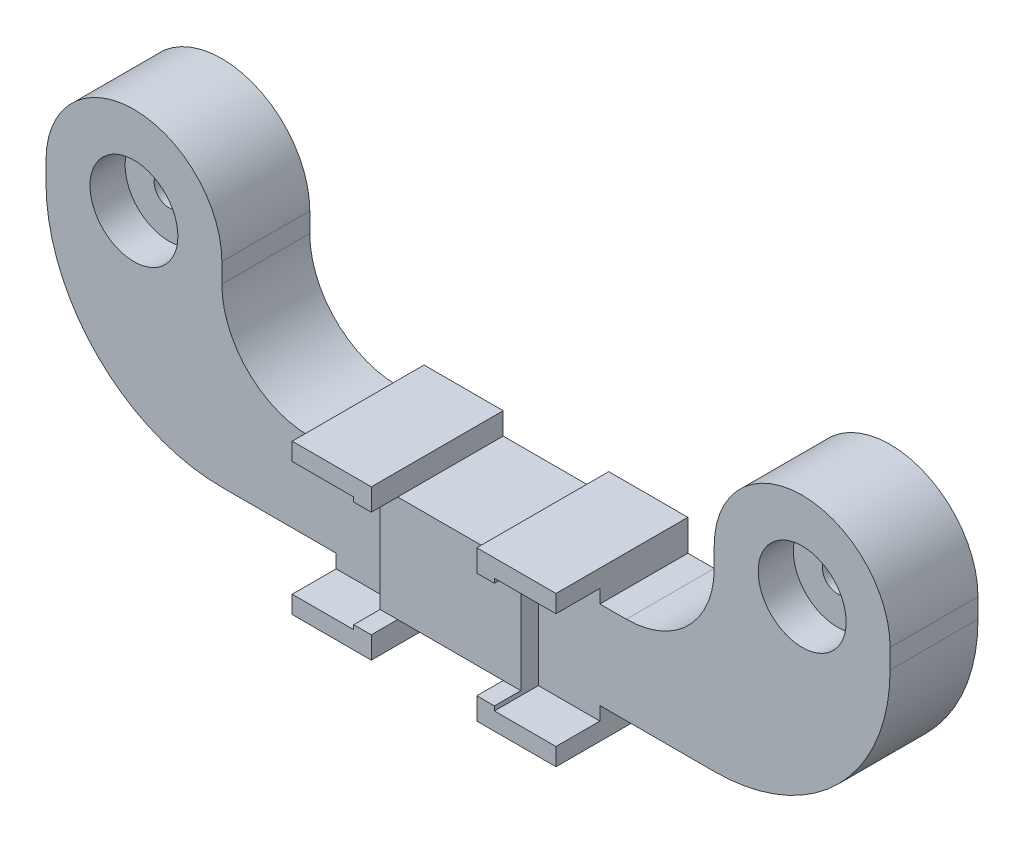
SolidWorks part; units mm, degrees
material "PETG"
ref_plane "Front Plane" through (0, 0, 0) normal (0, 0, 1) x (1, 0, 0)
ref_plane "Top Plane" through (0, 0, 0) normal (0, 1, 0) x (1, 0, 0)
ref_plane "Right Plane" through (0, 0, 0) normal (1, 0, 0) x (0, 0, -1)
sketch "Sketch1" plane through (0, 0, 0) normal (0, 0, 1) x (1, 0, 0)
  line L0 (-48, 20) -> (-48, 22.22)
  line L1 (28, 0) -> (-28, 0)
  line L2 (0, 0) -> (0, 10)
  line L3 (18, 10) -> (-18, 10)
  line L5 (0, 0.8051) -> (0, 50000.8051) construction
  line L6 (-28, 22.22) -> (-28, 20)
  line L7 (28, 22.22) -> (28, 20)
  line L8 (48, 20) -> (48, 22.22)
  circle A0 centre (-38, 22.22) radius 1.7
  arc A1 (-28, 22.22) -> (-48, 22.22) centre (-38, 22.22) ccw
  arc A2 (-18, 10) -> (-28, 20) centre (-18, 20) cw
  arc A3 (-28, 0) -> (-48, 20) centre (-28, 20) cw
  arc A4 (28, 0) -> (48, 20) centre (28, 20) ccw
  arc A5 (18, 10) -> (28, 20) centre (18, 20) ccw
  arc A6 (28, 22.22) -> (48, 22.22) centre (38, 22.22) cw
  circle A7 centre (38, 22.22) radius 1.7
  circle A8 centre (-38, 22.22) radius 5
  circle A9 centre (38, 22.22) radius 5
  dimension "D1" = 38
  dimension "D2" = 3.4
  dimension "D5" = 20
  dimension "D7" = 10
  dimension "D8" = 20
  dimension "D6" = 10
  dimension "D3" = 22.22
  dimension "D4" = 10
extrude "Boss-Extrude1" add sketch "Sketch1" against normal blind 10 contours A3 L1 L2 L3 A2 L6 A1 L0 A8 | A8 A0 | A6 L7 A5 L3 L2 L1 A4 L8 A9 | A9 A7 region at (-27.9027, 11.6824, 0) region at (27.9027, 11.6824, 0) region at (-42.8586, 22.22, 0) region at (33.1414, 22.22, 0)
extrude "Cut-Extrude1" cut sketch "Sketch1<4>" against normal blind 4 contours A8 A0 | A9 A7 region at (-42.8586, 22.22, 0) region at (33.1414, 22.22, 0)
sketch "Sketch1<4>" plane through (0, 0, 0) normal (0, 0, 1) x (1, 0, 0) same geometry as "Sketch1"
sketch "Sketch3" plane through (0, 0, 0) normal (0, 0, 1) x (1, 0, 0)
  line L0 (-6, 11.0375) -> (-6, -3.5375)
  line L5 (-15, 11.5375) -> (-8, 11.5375)
  line L6 (-15, 11.5375) -> (-15, -1.5375)
  line L7 (-15, -1.5375) -> (-8, -1.5375)
  line L8 (-8, 11.5375) -> (-8, -1.5375)
  line L10 (-15, 11.5375) -> (-15, 13.5375)
  line L11 (-15, 13.5375) -> (-6, 13.5375)
  line L12 (-6, 11.0375) -> (-6, 13.5375)
  line L14 (-15, -1.5375) -> (-15, -3.5375)
  line L15 (-15, -3.5375) -> (-6, -3.5375)
  line L17 (-6, -1.0375) -> (-8, -1.0375)
  line L18 (-6, 11.0375) -> (6, 11.0375)
  line L19 (-6, 11.0375) -> (-6, -1.0375)
  line L20 (-6, -1.0375) -> (6, -1.0375)
  line L21 (0, 11.0375) -> (0, -1.0375)
  line L22 (0, 0) -> (0, 50000) construction
  line L23 (-6, 11.0375) -> (-8, 11.0375)
  line L24 (28, 0) -> (-28, 0) construction
  line L25 (6, 11.0375) -> (8, 11.0375)
  line L26 (6, 11.0375) -> (6, -1.0375)
  line L27 (6, -1.0375) -> (8, -1.0375)
  line L28 (15, -3.5375) -> (6, -3.5375)
  line L29 (15, -1.5375) -> (15, -3.5375)
  line L30 (6, 11.0375) -> (6, 13.5375)
  line L31 (15, 13.5375) -> (6, 13.5375)
  line L32 (15, 11.5375) -> (15, 13.5375)
  line L33 (8, 11.5375) -> (8, -1.5375)
  line L34 (15, -1.5375) -> (8, -1.5375)
  line L35 (15, 11.5375) -> (15, -1.5375)
  line L36 (15, 11.5375) -> (8, 11.5375)
  line L37 (6, 11.0375) -> (6, -3.5375)
  point P13 (0, 5)
  point P20 (0, 0)
  line M5 (-28, 0) -> (28, 0)
  line M11 (18, 10) -> (-18, 10)
  dimension "D1" = 15
  dimension "D2" = 13.075
  dimension "D3" = 5
  dimension "D4" = 2
  dimension "D5" = 0.5
  dimension "D6" = 0.5
  dimension "D7" = 7
extrude "Boss-Extrude2" add sketch "Sketch3" against normal through all contours L21 L18 L0 M11 | L26 L18 L21 M11 | L21 L0 L20 M5 | L26 L21 L20 M5 | L0 L23 L8 M11 | L8 L5 L6 M11 | L23 L12 L11 L10 L5 L8 | L0 L17 L8 L7 L14 L15 | L17 L0 L8 M5 | L33 L26 L27 M5 | L27 L37 L28 L29 L34 L33 | L35 L33 L34 M5 | L35 L36 L33 M11 | L33 L25 L26 M11 | L36 L32 L31 L30 L25 L33 | L8 L6 L7 M5 region at (-7, -0.5188, 0) region at (-10.3158, -2.4717, 0) region at (-3, -0.5188, 0) region at (-11.5, -0.7688, 0) region at (3, -0.5188, 0) region at (-7, 10.5187, 0) region at (-3, 10.5187, 0) region at (7, -0.5187, 0) region at (10.3158, -2.4717, 0) region at (-10.3158, 12.4717, 0) region at (3, 10.5187, 0) region at (-11.5, 10.7687, 0) region at (11.5, -0.7688, 0) region at (7, 10.5187, 0) region at (10.3158, 12.4717, 0) region at (11.5, 10.7687, 0)
extrude "Boss-Extrude3" add sketch "Sketch3<3>" along normal blind 5 contours L23 L12 L11 L10 L5 L8 | L0 L17 L8 L7 L14 L15 | L27 L37 L28 L29 L34 L33 | L36 L32 L31 L30 L25 L33 region at (-10.3158, 12.4717, 0) region at (-10.3158, -2.4717, 0) region at (10.3158, 12.4717, 0) region at (10.3158, -2.4717, 0)
sketch "Sketch3<3>" plane through (0, 0, 0) normal (0, 0, 1) x (1, 0, 0) same geometry as "Sketch3"
extrude "Boss-Extrude4" add sketch "Sketch3<4>" along normal blind 2 contours L8 L0 M11 M5 | L21 L0 M11 M5 | L33 L26 M11 M5 | L26 L21 M11 M5 | L26 L18 L21 M11 | L33 L25 L26 M11 | L21 L18 L0 M11 | L0 L23 L8 M11 | L17 L0 L8 M5 | L21 L0 L20 M5 | L26 L21 L20 M5 | L33 L26 L27 M5 region at (-7, -0.5188, 0) region at (-3, -0.5188, 0) region at (-7, 5, 0) region at (-3, 5, 0) region at (3, -0.5188, 0) region at (-7, 10.5187, 0) region at (-3, 10.5187, 0) region at (3, 5, 0) region at (7, -0.5187, 0) region at (3, 10.5187, 0) region at (7, 5, 0) region at (7, 10.5187, 0)
sketch "Sketch3<4>" plane through (0, 0, 0) normal (0, 0, 1) x (1, 0, 0) same geometry as "Sketch3"
equation "\"tol_dia_id_intfc\" = 0.0500mm ' For hole diameters - Interference fit"
equation "\"tol_dia_id_slip\"  = 0.0750mm ' For hole diameters - Slip fit"
equation "\"tol_dia_id_clear\" = 0.1000mm ' For hole diameters - Clearance fit"
equation "\"tol_dia_od_intfc\" = 0.0500mm ' For shaft diameters - Interference fit"
equation "\"tol_dia_od_slip\"  = 0.0750mm ' For shaft diameters - Slip fit"
equation "\"tol_dia_od_clear\" = 0.1000mm ' For shaft diameters - Clearance fit"
equation "\"tol_general_intfc\"= 0.0250mm ' For general parts (Horiz) - Interference fit"
equation "\"tol_general_slip\" = 0.0375mm ' For general parts (Horiz) - Slip fit"
equation "\"tol_general_clear\"= 0.0500mm ' For general parts (Horiz) - Clearance fit"
equation "\"tol_layer_intfc\"  = 0.0250mm ' For all parts (Vert) - Interference fit"
equation "\"tol_layer_slip\"   = 0.0375mm ' For all parts (Vert) - Slip fit"
equation "\"tol_layer_clear\"  = 0.0500mm ' For all parts (Vert) - Clearance fit"
equation "\"tol_corner_rad\"   = 0.100mm ' For corners that fit into other parts"
equation "\"D2@Sketch3\"=13mm+\"tol_general_slip\"*2"
equation "\"D6@Sketch3\"=\"D5@Sketch3\""
